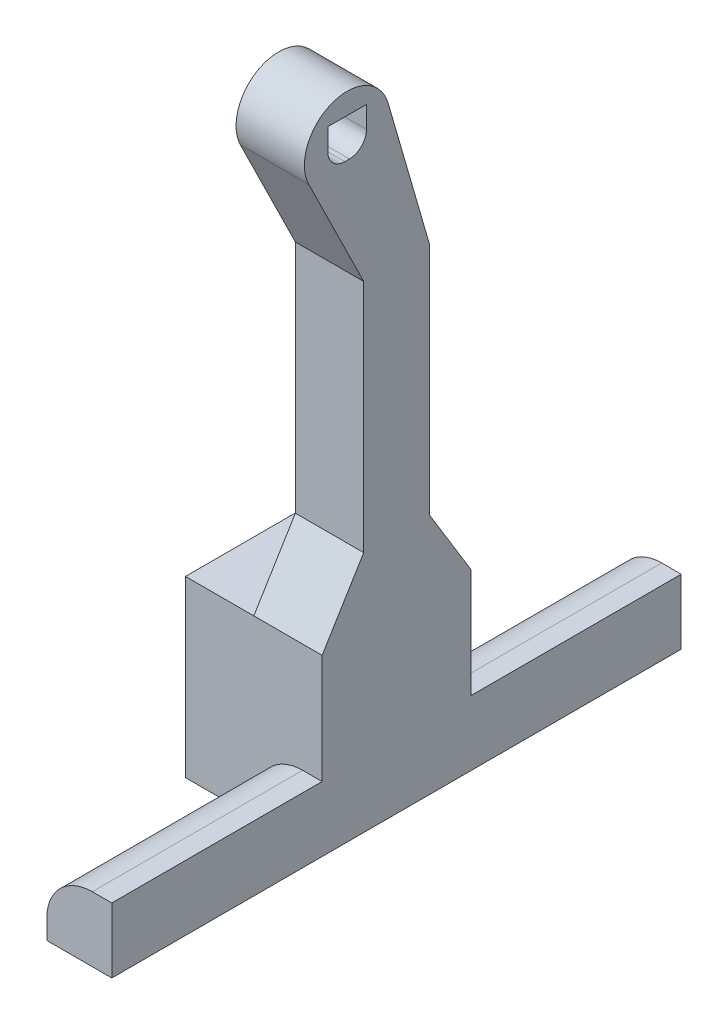
SolidWorks part; units mm, degrees
ref_plane "Front Plane" through (0, 0, 0) normal (0, 0, 1) x (1, 0, 0)
ref_plane "Top Plane" through (0, 0, 0) normal (0, 1, 0) x (1, 0, 0)
ref_plane "Right Plane" through (0, 0, 0) normal (1, 0, 0) x (0, 0, -1)
sketch "Sketch1" plane through (0, 0, 0) normal (1, 0, 0) x (0, 0, -1)
  line L0 (-3, 9.82) -> (-3, 0)
  line L1 (-3, 0) -> (-6.5301, 0)
  line L2 (-6.5301, 0) -> (-6.5301, 9.82)
  line L3 (-6.5301, 15.3053) -> (-2.8793, 21.2873)
  line L4 (-2.8793, 21.2873) -> (-2.8793, 41.9106)
  line L5 (0, 0) -> (0, 50000) construction
  line L6 (2.8793, 21.2873) -> (2.8793, 41.9106)
  line L7 (6.5301, 15.3053) -> (2.8793, 21.2873)
  line L8 (6.5301, 0) -> (6.5301, 9.82)
  line L9 (3, 0) -> (6.5301, 0)
  line L10 (3, 9.82) -> (3, 0)
  line L11 (-3, 9.82) -> (3, 9.82)
  line L12 (-4.5363, 52.0529) -> (-4.1363, 52.0529) construction
  line L13 (-4.5363, 53.3529) -> (-4.1363, 53.3529) construction
  line L14 (-5.8363, 55.0529) -> (-5.8363, 53.3529) construction
  line L15 (-2.8363, 53.3529) -> (-2.8363, 55.0529) construction
  line L16 (-2.8363, 55.0529) -> (-5.8363, 55.0529) construction
  line L17 (-5.8363, 55.0529) -> (-2.8363, 55.0529) construction
  line L18 (-4.5363, 52.0529) -> (-4.1363, 52.0529) construction
  line L19 (-5.8363, 55.0529) -> (-5.8363, 53.3529) construction
  line L20 (-2.8363, 53.3529) -> (-2.8363, 55.0529) construction
  line L21 (-2.8363, 55.0529) -> (-5.8363, 55.0529) construction
  line L22 (-5.8363, 55.0529) -> (-2.8363, 55.0529)
  line L23 (-2.8793, 41.9106) -> (-7.7007, 51.6951)
  line L24 (2.8793, 41.9106) -> (-0.7333, 54.3955)
  line L25 (6.5301, 9.82) -> (6.5301, 15.3053)
  line L26 (-6.5301, 9.82) -> (-6.5301, 15.3053)
  line L27 (-6.5301, 9.82) -> (-3, 9.82)
  line L28 (3, 9.82) -> (6.5301, 9.82)
  line L29 (3, 0) -> (-3, 0)
  line L30 (6.5301, 15.3053) -> (-6.5301, 15.3053)
  line L31 (-2.6363, 55.2529) -> (-6.0363, 55.2529)
  line L32 (-6.0363, 55.2529) -> (-6.0363, 53.3529)
  line L33 (-4.5363, 51.8529) -> (-4.1363, 51.8529)
  line L34 (-2.6363, 53.3529) -> (-2.6363, 55.2529)
  line L35 (-25, 12.1535) -> (-25, -1.9655) construction
  line L36 (25, 12.1535) -> (25, -1.9655) construction
  arc A0 (-4.1363, 52.0529) -> (-2.8363, 53.3529) centre (-4.1363, 53.3529) ccw construction
  arc A1 (-5.8363, 53.3529) -> (-4.5363, 52.0529) centre (-4.5363, 53.3529) ccw construction
  arc A2 (-4.1363, 52.0529) -> (-2.8363, 53.3529) centre (-4.1363, 53.3529) ccw construction
  arc A3 (-5.8363, 53.3529) -> (-4.5363, 52.0529) centre (-4.5363, 53.3529) ccw construction
  arc A4 (-7.7007, 51.6951) -> (-0.7333, 54.3955) centre (-4.3363, 53.3529) cw
  arc A5 (-6.0363, 53.3529) -> (-4.5363, 51.8529) centre (-4.5363, 53.3529) ccw
  arc A6 (-4.1363, 51.8529) -> (-2.6363, 53.3529) centre (-4.1363, 53.3529) ccw
  dimension "D3" = 0.2
  dimension "D1" = 6
  dimension "D2" = 9.82
  dimension "D4" = 25
extrude "Boss-Extrude2" add sketch "Sketch1" against normal blind 6 contours L28 L10 L9 L8 | L27 L2 L1 L0 | L25 L30 L26 L27 L11 L28 region at (0, 12.5626, 0) region at (0, 4.91, 4.7651) region at (0, 4.91, -4.7651)
extrude "Boss-Extrude3" add sketch "Sketch1<4>" along normal blind 6 contours L29 L10 L11 L0 | L27 L2 L1 L0 | L28 L10 L9 L8 | L25 L30 L26 L27 L11 L28 | A4 L23 L4 L3 L30 L7 L6 L24 A3 L19 L21 L20 A2 L18 region at (0, 4.91, 0) region at (0, 12.5626, 0) region at (0, 4.91, 4.7651) region at (0, 4.91, -4.7651) region at (0, 34.6215, 0.8851)
sketch "Sketch1<4>" plane through (0, 0, 0) normal (1, 0, 0) x (0, 0, -1) same geometry as "Sketch1"
sketch "Sketch4" plane through (0, 0, 6.5301) normal (0, 0, 1) x (1, 0, 0)
  line L1 (6, 0) -> (0.2928, 0)
  line L2 (6, 0) -> (6, 5.7072)
  line L3 (6, 5.7072) -> (4.2928, 5.7072)
  line L4 (0.2928, 0) -> (0.2928, 1.7072)
  arc A0 (0.2928, 1.7072) -> (4.2928, 5.7072) centre (4.2928, 1.7072) cw
  dimension "D1" = 4
extrude "Boss-Extrude4" add sketch "Sketch4" along normal up to vertex (18.4699 mm away) and the other way up to vertex (31.5301 mm away) up to point (0, -1.9655, 25) other way up to point (0, -1.9655, -25)
